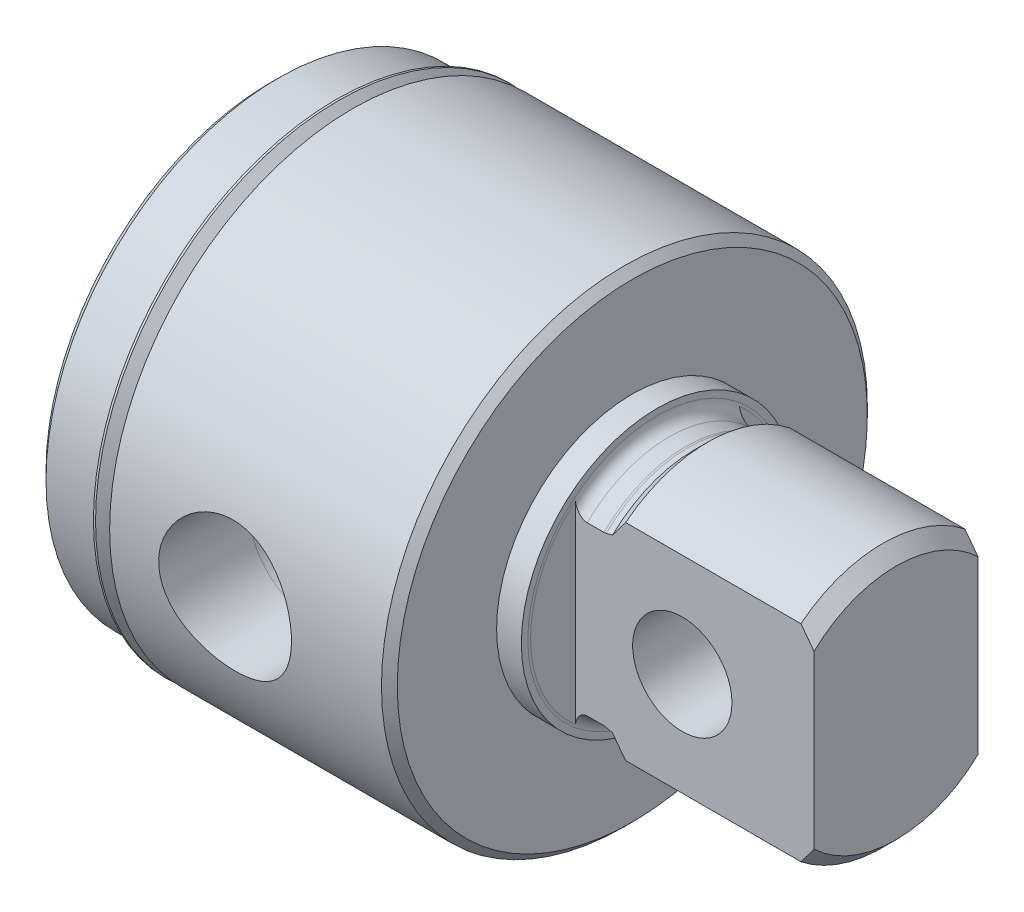
SolidWorks part; units mm, degrees
material "Cast Alloy Steel"
ref_plane "Front Plane" through (0, 0, 0) normal (0, 0, 1) x (1, 0, 0)
ref_plane "Top Plane" through (0, 0, 0) normal (0, 1, 0) x (1, 0, 0)
ref_plane "Right Plane" through (0, 0, 0) normal (1, 0, 0) x (0, 0, -1)
ref_plane "Plane1" through (60.325, 0, 0) normal (1, 0, 0) x (0, 0, -1)
sketch "Sketch1" plane through (0, 0, 0) normal (0, 0, 1) x (1, 0, 0)
  line L0 (0, 0) -> (0, 21.6345)
  line L1 (0, 21.6345) -> (0.762, 22.3965)
  line L2 (0.762, 22.3965) -> (5.8166, 22.3965)
  line L3 (5.8166, 22.3965) -> (6.8707, 21.3423)
  line L4 (6.8707, 21.3423) -> (7.9248, 21.3423)
  line L5 (7.9248, 21.3423) -> (7.9248, 23.4251)
  line L6 (7.9248, 23.4251) -> (34.1376, 23.4251)
  line L7 (34.1376, 23.4251) -> (34.8996, 22.6632)
  line L8 (34.8996, 22.6632) -> (34.8996, 0)
  line L9 (34.8996, 0) -> (0, 0)
  line L10 (34.8996, 0) -> (0, 0) construction
revolve "Revolve1" add sketch "Sketch1" angle 360 about L10 reverse direction yes
sketch "Sketch2" plane through (0, 0, 0) normal (0, 0, 1) x (1, 0, 0)
  line L0 (34.8996, 0) -> (34.8996, 13.0874)
  line L1 (34.8996, 13.0874) -> (37.2872, 13.0874)
  line L2 (37.2872, 13.0874) -> (37.2872, 12.4651)
  line L3 (38.4556, 11.2967) -> (40.0685, 11.2967)
  line L4 (40.284, 11.3167) -> (40.8947, 11.4313)
  line L5 (40.8947, 11.4313) -> (42.1634, 12.7)
  line L6 (42.1634, 12.7) -> (59.0563, 12.7)
  line L7 (59.0563, 12.7) -> (60.325, 11.4313)
  line L8 (60.325, 11.4313) -> (60.325, 0)
  line L9 (60.325, 0) -> (34.8996, 0)
  line L10 (60.325, 0) -> (34.8996, 0) construction
  arc A0 (37.2872, 12.4651) -> (38.4556, 11.2967) centre (38.4556, 12.4651) ccw
  arc A1 (40.0685, 11.2967) -> (40.284, 11.3167) centre (40.0685, 12.465) ccw
revolve "Revolve2" add sketch "Sketch2" angle 360 about L10 reverse direction yes
cosmetic thread "Cosmetic Thread1" parameters "D1"=19.4303, "D2"=22.8625
sketch "Sketch3" plane through (60.325, 0, 0) normal (1, 0, 0) x (0, 0, -1)
  line L0 (-46.8503, -93.7006) -> (46.8503, -93.7006)
  line L1 (46.8503, -93.7006) -> (46.8503, 93.7006)
  line L2 (46.8503, 93.7006) -> (-46.8503, 93.7006)
  line L3 (-46.8503, 93.7006) -> (-46.8503, -93.7006)
  line L4 (-7.9057, -46.8503) -> (7.9057, -46.8503)
  line L5 (7.9057, -46.8503) -> (7.9057, 46.8503)
  line L6 (7.9057, 46.8503) -> (-7.9057, 46.8503)
  line L7 (-7.9057, 46.8503) -> (-7.9057, -46.8503)
extrude "Cut-Extrude1" cut sketch "Sketch3" against normal blind 23.0124
ref_plane "Plane2" through (34.8996, 0, 0) normal (1, 0, 0) x (0, 0, -1)
hole_wizard "Hole1" positions "Sketch5" profile "Sketch4" legacy
sketch "Sketch5" plane through (0, 0, 0) normal (-1, 0, 0) x (0, 0, 1)
  point P0 (0, 0)
sketch "Sketch4" plane through (0, 0, 0) normal (0, 1, 0) x (0, 0, 1)
  line L0 (0, 0) -> (0, 33.8939)
  line L1 (0, 33.8939) -> (10.3124, 27.94)
  line L2 (10.3124, 27.94) -> (10.3124, 0)
  line L4 (10.3124, 0) -> (0, 0)
  line L6 (0, 33.8939) -> (-10.3124, 27.94) construction
  line L7 (0, -4.2442) -> (0, 117.3081) construction
  dimension "Diameter" = 20.6248
  dimension "Depth" = 27.94
  dimension "Drill Angle" = 120
ref_plane "Plane3" through (0, 0, 0) normal (0, 0.9998, 0.0175) x (1, 0, 0)
sketch "Sketch6" plane through (0, 0, 0) normal (0, 0.9998, 0.0175) x (1, 0, 0)
  line L0 (19.05, 0) -> (25.188, 0)
  line L1 (25.188, 0) -> (25.188, -14.9669)
  line L2 (25.188, -14.9669) -> (25.452, -23.4251)
  line L3 (25.452, -23.4251) -> (19.05, -23.4251)
  line L4 (19.05, -23.4251) -> (19.05, 0)
  line L5 (19.05, -23.4251) -> (19.05, 0) construction
revolve "Cut-Revolve1" cut sketch "Sketch6" angle 360 about L5 reverse direction yes
cosmetic thread "Cosmetic Thread2" parameters "D1"=8.4582, "D2"=13.716
ref_plane "Plane4" through (19.05, 0, 0) normal (1, 0, 0) x (0, 0, -1)
sketch "Sketch7" plane through (0, 0, 0) normal (0, 0, 1) x (1, 0, 0)
  line L0 (0, 0) -> (0, 12.7)
  line L1 (0, 12.7) -> (10.3124, 12.7)
  line L2 (10.3124, 12.7) -> (10.3124, 0)
  line L3 (10.3124, 0) -> (0, 0)
  line L4 (10.3124, 0) -> (0, 0) construction
revolve "Cut-Revolve2" cut sketch "Sketch7" angle 360 about L4 reverse direction yes
ref_plane "Plane5" through (6.8707, 0, 0) normal (1, 0, 0) x (0, 0, -1)
sketch "Sketch8" plane through (0, 0, 0) normal (0, 0, 1) x (1, 0, 0)
  line L0 (6.3628, 23.341) -> (7.7898, 21.914)
  line L1 (7.7898, 21.7344) -> (7.3978, 21.3424)
  line L2 (7.3978, 21.3424) -> (6.8707, 21.3424)
  line L3 (6.8707, 21.3424) -> (6.8707, 21.0884)
  line L4 (6.8707, 21.0884) -> (7.9248, 21.0884)
  line L5 (7.9248, 21.0884) -> (7.9248, 22.0663)
  line L6 (7.9248, 22.0663) -> (6.566, 23.4251)
  line L7 (6.566, 23.4251) -> (6.3628, 23.4251)
  line L8 (6.3628, 23.4251) -> (6.3628, 23.341)
  line L9 (7.9248, 0) -> (6.8707, 0) construction
  arc A0 (7.7898, 21.914) -> (7.7898, 21.7344) centre (7.7, 21.8242) cw
revolve "Revolve3" add sketch "Sketch8" angle 360 about L9 reverse direction yes
ref_plane "Plane6" through (60.452, 0, 0) normal (1, 0, 0) x (0, 0, -1)
sketch "Sketch9" plane through (0, 0, 0) normal (0, 0, 1) x (1, 0, 0)
  circle A0 centre (47.625, 0) radius 4.7879
extrude "Cut-Extrude2" cut sketch "Sketch9" along normal blind 11.8586 and the other way blind 11.8586
ref_plane "Plane7" through (37.2872, 0, 0) normal (1, 0, 0) x (0, 0, -1)
ref_plane "Plane8" through (53.975, 0, 0) normal (1, 0, 0) x (0, 0, -1)
ref_plane "Plane9" through (47.625, 0, 0) normal (1, 0, 0) x (0, 0, -1)
ref_plane "Plane10" through (60.325, 0, 0) normal (1, 0, 0) x (0, 0, -1)
ref_plane "Plane11" through (0, 0, 0) normal (0, 0, 1) x (1, 0, 0)
ref_plane "Plane12" through (37.2872, 0, 0) normal (1, 0, 0) x (0, 0, -1)
ref_plane "Plane13" through (0, 0, 0) normal (0, 1, 0) x (1, 0, 0)
ref_plane "Plane14" through (0, 0, 0) normal (0, 1, 0) x (1, 0, 0)
ref_plane "Plane15" through (34.8996, 0, 0) normal (1, 0, 0) x (0, 0, -1)
ref_plane "1 XY" through (37.2872, 0, 0) normal (1, 0, 0) x (0, 0, -1)
ref_plane "1 XZ" through (0, 0, 0) normal (0, -1, 0) x (-1, 0, 0)
ref_plane "1 YZ" through (0, 0, 0) normal (0, 0, -1) x (-1, 0, 0)
ref_axis "1 X" through (37.2872, 0, 80.9) along (0, 0, -1)
ref_axis "1 Y" through (37.2872, -50, 0) along (0, 1, 0)
ref_axis "1 Z" through (80.9, 0, 0) along (-1, 0, 0)
sketch3d "1"
  point P0 (37.2872, 0, 0)
ref_plane "c1 XY" through (0, 0, 0) normal (0, 0, 1) x (1, 0, 0)
ref_plane "c1 XZ" through (0, 13.0874, 0) normal (0, -1, 0) x (-1, 0, 0)
ref_plane "c1 YZ" through (34.8996, 0, 0) normal (1, 0, 0) x (0, 0, -1)
ref_axis "c1 X" through (-80.9, 13.0874, 0) along (1, 0, 0)
ref_axis "c1 Y" through (34.8996, -50, 0) along (0, 1, 0)
ref_axis "c1 Z" through (34.8996, 13.0874, 80.9) along (0, 0, -1)
sketch3d "c1"
  point P0 (34.8996, 13.0874, 0)
ref_plane "c2 XY" through (0, 0, 0) normal (0, 0, 1) x (1, 0, 0)
ref_plane "c2 XZ" through (0, -13.0874, 0) normal (0, -1, 0) x (-1, 0, 0)
ref_plane "c2 YZ" through (34.8996, 0, 0) normal (1, 0, 0) x (0, 0, -1)
ref_axis "c2 X" through (-80.9, -13.0874, 0) along (1, 0, 0)
ref_axis "c2 Y" through (34.8996, -50, 0) along (0, 1, 0)
ref_axis "c2 Z" through (34.8996, -13.0874, 80.9) along (0, 0, -1)
sketch3d "c2"
  point P0 (34.8996, -13.0874, 0)
ref_plane "cc1 XY" through (0, 0, 0) normal (0, 0, 1) x (1, 0, 0)
ref_plane "cc1 XZ" through (0, 0, 0) normal (0, -1, 0) x (-1, 0, 0)
ref_plane "cc1 YZ" through (34.8996, 0, 0) normal (1, 0, 0) x (0, 0, -1)
ref_axis "cc1 X" through (-80.9, 0, 0) along (1, 0, 0)
ref_axis "cc1 Y" through (34.8996, -50, 0) along (0, 1, 0)
ref_axis "cc1 Z" through (34.8996, 0, 80.9) along (0, 0, -1)
sketch3d "cc1"
  point P0 (34.8996, 0, 0)
ref_plane "cc2 XY" through (0, 0, 0) normal (0, 0, 1) x (1, 0, 0)
ref_plane "cc2 XZ" through (0, 0, 0) normal (0, -1, 0) x (-1, 0, 0)
ref_plane "cc2 YZ" through (37.2872, 0, 0) normal (1, 0, 0) x (0, 0, -1)
ref_axis "cc2 X" through (-80.9, 0, 0) along (1, 0, 0)
ref_axis "cc2 Y" through (37.2872, -50, 0) along (0, 1, 0)
ref_axis "cc2 Z" through (37.2872, 0, 80.9) along (0, 0, -1)
sketch3d "cc2"
  point P0 (37.2872, 0, 0)
ref_plane "lovra1 XY" through (53.975, 0, 0) normal (1, 0, 0) x (0, 0, -1)
ref_plane "lovra1 XZ" through (0, 0, 0) normal (0, -1, 0) x (-1, 0, 0)
ref_plane "lovra1 YZ" through (0, 0, 0) normal (0, 0, -1) x (-1, 0, 0)
ref_axis "lovra1 X" through (53.975, 0, 80.9) along (0, 0, -1)
ref_axis "lovra1 Y" through (53.975, -50, 0) along (0, 1, 0)
ref_axis "lovra1 Z" through (80.9, 0, 0) along (-1, 0, 0)
sketch3d "lovra1"
  point P0 (53.975, 0, 0)
ref_plane "lovra2 XY" through (53.975, 0, 0) normal (1, 0, 0) x (0, 0, -1)
ref_plane "lovra2 XZ" through (0, 15.748, 0) normal (0, -1, 0) x (-1, 0, 0)
ref_plane "lovra2 YZ" through (0, 0, 0) normal (0, 0, -1) x (-1, 0, 0)
ref_axis "lovra2 X" through (53.975, 15.748, 80.9) along (0, 0, -1)
ref_axis "lovra2 Y" through (53.975, -50, 0) along (0, 1, 0)
ref_axis "lovra2 Z" through (80.9, 15.748, 0) along (-1, 0, 0)
sketch3d "lovra2"
  point P0 (53.975, 15.748, 0)
ref_plane "lovra21 XY" through (0, 0, 0) normal (1, 0, 0) x (0, 0, -1)
ref_plane "lovra21 XZ" through (0, 0, 0) normal (0, -1, 0) x (-1, 0, 0)
ref_plane "lovra21 YZ" through (0, 0, 5.2705) normal (0, 0, -1) x (-1, 0, 0)
ref_axis "lovra21 X" through (0, 0, 80.9) along (0, 0, -1)
ref_axis "lovra21 Y" through (0, -50, 5.2705) along (0, 1, 0)
ref_axis "lovra21 Z" through (80.9, 0, 5.2705) along (-1, 0, 0)
sketch3d "lovra21"
  point P0 (0, 0, 5.2705)
ref_plane "lovra22 XY" through (0, 0, 0) normal (1, 0, 0) x (0, 0, -1)
ref_plane "lovra22 XZ" through (0, 0, 0) normal (0, -1, 0) x (-1, 0, 0)
ref_plane "lovra22 YZ" through (0, 0, -5.2705) normal (0, 0, -1) x (-1, 0, 0)
ref_axis "lovra22 X" through (0, 0, 80.9) along (0, 0, -1)
ref_axis "lovra22 Y" through (0, -50, -5.2705) along (0, 1, 0)
ref_axis "lovra22 Z" through (80.9, 0, -5.2705) along (-1, 0, 0)
sketch3d "lovra22"
  point P0 (0, 0, -5.2705)
ref_plane "lovra3 XY" through (53.975, 0, 0) normal (1, 0, 0) x (0, 0, -1)
ref_plane "lovra3 XZ" through (0, -15.748, 0) normal (0, -1, 0) x (-1, 0, 0)
ref_plane "lovra3 YZ" through (0, 0, 0) normal (0, 0, -1) x (-1, 0, 0)
ref_axis "lovra3 X" through (53.975, -15.748, 80.9) along (0, 0, -1)
ref_axis "lovra3 Y" through (53.975, -50, 0) along (0, 1, 0)
ref_axis "lovra3 Z" through (80.9, -15.748, 0) along (-1, 0, 0)
sketch3d "lovra3"
  point P0 (53.975, -15.748, 0)
ref_plane "olen XY" through (47.625, 0, 0) normal (1, 0, 0) x (0, 0, -1)
ref_plane "olen XZ" through (0, 0, 0) normal (0, -1, 0) x (-1, 0, 0)
ref_plane "olen YZ" through (0, 0, 0) normal (0, 0, -1) x (-1, 0, 0)
ref_axis "olen X" through (47.625, 0, 80.9) along (0, 0, -1)
ref_axis "olen Y" through (47.625, -50, 0) along (0, 1, 0)
ref_axis "olen Z" through (80.9, 0, 0) along (-1, 0, 0)
sketch3d "olen"
  point P0 (47.625, 0, 0)
ref_plane "p1 XY" through (60.325, 0, 0) normal (1, 0, 0) x (0, 0, -1)
ref_plane "p1 XZ" through (0, 0, 0) normal (0, -1, 0) x (-1, 0, 0)
ref_plane "p1 YZ" through (0, 0, 7.9057) normal (0, 0, -1) x (-1, 0, 0)
ref_axis "p1 X" through (60.325, 0, 80.9) along (0, 0, -1)
ref_axis "p1 Y" through (60.325, -50, 7.9057) along (0, 1, 0)
ref_axis "p1 Z" through (80.9, 0, 7.9057) along (-1, 0, 0)
sketch3d "p1"
  point P0 (60.325, 0, 7.9057)
ref_plane "p2 XY" through (60.325, 0, 0) normal (1, 0, 0) x (0, 0, -1)
ref_plane "p2 XZ" through (0, 0, 0) normal (0, -1, 0) x (-1, 0, 0)
ref_plane "p2 YZ" through (0, 0, -7.9057) normal (0, 0, -1) x (-1, 0, 0)
ref_axis "p2 X" through (60.325, 0, 80.9) along (0, 0, -1)
ref_axis "p2 Y" through (60.325, -50, -7.9057) along (0, 1, 0)
ref_axis "p2 Z" through (80.9, 0, -7.9057) along (-1, 0, 0)
sketch3d "p2"
  point P0 (60.325, 0, -7.9057)
ref_plane "port XY" through (0, 0, 0) normal (0, 0, 1) x (1, 0, 0)
ref_plane "port XZ" through (0, 0, 0) normal (0, -1, 0) x (-1, 0, 0)
ref_plane "port YZ" through (19.05, 0, 0) normal (1, 0, 0) x (0, 0, -1)
ref_axis "port X" through (-80.9, 0, 0) along (1, 0, 0)
ref_axis "port Y" through (19.05, -50, 0) along (0, 1, 0)
ref_axis "port Z" through (19.05, 0, 80.9) along (0, 0, -1)
sketch3d "port"
  point P0 (19.05, 0, 0)
ref_plane "port2 XY" through (60.325, 0, 0) normal (1, 0, 0) x (0, 0, -1)
ref_plane "port2 XZ" through (0, 0, 0) normal (0, -1, 0) x (-1, 0, 0)
ref_plane "port2 YZ" through (0, 0, 0) normal (0, 0, -1) x (-1, 0, 0)
ref_axis "port2 X" through (60.325, 0, 80.9) along (0, 0, -1)
ref_axis "port2 Y" through (60.325, -50, 0) along (0, 1, 0)
ref_axis "port2 Z" through (80.9, 0, 0) along (-1, 0, 0)
sketch3d "port2"
  point P0 (60.325, 0, 0)
ref_plane "thd1 XY" through (60.325, 0, 0) normal (1, 0, 0) x (0, 0, -1)
ref_plane "thd1 XZ" through (0, 0, 0) normal (0, -1, 0) x (-1, 0, 0)
ref_plane "thd1 YZ" through (0, 0, 12.7) normal (0, 0, -1) x (-1, 0, 0)
ref_axis "thd1 X" through (60.325, 0, 80.9) along (0, 0, -1)
ref_axis "thd1 Y" through (60.325, -50, 12.7) along (0, 1, 0)
ref_axis "thd1 Z" through (80.9, 0, 12.7) along (-1, 0, 0)
sketch3d "thd1"
  point P0 (60.325, 0, 12.7)
ref_plane "thd2 XY" through (60.325, 0, 0) normal (1, 0, 0) x (0, 0, -1)
ref_plane "thd2 XZ" through (0, 0, 0) normal (0, -1, 0) x (-1, 0, 0)
ref_plane "thd2 YZ" through (0, 0, -12.7) normal (0, 0, -1) x (-1, 0, 0)
ref_axis "thd2 X" through (60.325, 0, 80.9) along (0, 0, -1)
ref_axis "thd2 Y" through (60.325, -50, -12.7) along (0, 1, 0)
ref_axis "thd2 Z" through (80.9, 0, -12.7) along (-1, 0, 0)
sketch3d "thd2"
  point P0 (60.325, 0, -12.7)
ref_plane "to_mounting_bracket XY" through (34.8996, 0, 0) normal (1, 0, 0) x (0, 0, -1)
ref_plane "to_mounting_bracket XZ" through (0, 0, 0) normal (0, -1, 0) x (-1, 0, 0)
ref_plane "to_mounting_bracket YZ" through (0, 0, 0) normal (0, 0, -1) x (-1, 0, 0)
ref_axis "to_mounting_bracket X" through (34.8996, 0, 80.9) along (0, 0, -1)
ref_axis "to_mounting_bracket Y" through (34.8996, -50, 0) along (0, 1, 0)
ref_axis "to_mounting_bracket Z" through (80.9, 0, 0) along (-1, 0, 0)
sketch3d "to_mounting_bracket"
  point P0 (34.8996, 0, 0)
ref_plane "to_nut XY" through (37.2872, 0, 0) normal (1, 0, 0) x (0, 0, -1)
ref_plane "to_nut XZ" through (0, 0, 0) normal (0, -1, 0) x (-1, 0, 0)
ref_plane "to_nut YZ" through (0, 0, 0) normal (0, 0, -1) x (-1, 0, 0)
ref_axis "to_nut X" through (37.2872, 0, 80.9) along (0, 0, -1)
ref_axis "to_nut Y" through (37.2872, -50, 0) along (0, 1, 0)
ref_axis "to_nut Z" through (80.9, 0, 0) along (-1, 0, 0)
sketch3d "to_nut"
  point P0 (37.2872, 0, 0)
ref_plane "to_pin XY" through (0, 0, 0) normal (0, 0, 1) x (1, 0, 0)
ref_plane "to_pin XZ" through (0, 0, 0) normal (0, -1, 0) x (-1, 0, 0)
ref_plane "to_pin YZ" through (47.625, 0, 0) normal (1, 0, 0) x (0, 0, -1)
ref_axis "to_pin X" through (-80.9, 0, 0) along (1, 0, 0)
ref_axis "to_pin Y" through (47.625, -50, 0) along (0, 1, 0)
ref_axis "to_pin Z" through (47.625, 0, 80.9) along (0, 0, -1)
sketch3d "to_pin"
  point P0 (47.625, 0, 0)
ref_plane "to_screw XY" through (0, 0, 0) normal (0, 1, 0) x (1, 0, 0)
ref_plane "to_screw XZ" through (0, 0, 0) normal (0, 0, 1) x (1, 0, 0)
ref_plane "to_screw YZ" through (19.05, 0, 0) normal (1, 0, 0) x (0, 0, -1)
ref_axis "to_screw X" through (-80.9, 0, 0) along (1, 0, 0)
ref_axis "to_screw Y" through (19.05, 0, 50) along (0, 0, -1)
ref_axis "to_screw Z" through (19.05, 50, 0) along (0, -1, 0)
sketch3d "to_screw"
  point P0 (19.05, 0, 0)
ref_plane "to_tube XY" through (6.8707, 0, 0) normal (1, 0, 0) x (0, 0, -1)
ref_plane "to_tube XZ" through (0, 0, 0) normal (0, -1, 0) x (-1, 0, 0)
ref_plane "to_tube YZ" through (0, 0, 0) normal (0, 0, -1) x (-1, 0, 0)
ref_axis "to_tube X" through (6.8707, 0, 80.9) along (0, 0, -1)
ref_axis "to_tube Y" through (6.8707, -50, 0) along (0, 1, 0)
ref_axis "to_tube Z" through (80.9, 0, 0) along (-1, 0, 0)
sketch3d "to_tube"
  point P0 (6.8707, 0, 0)
